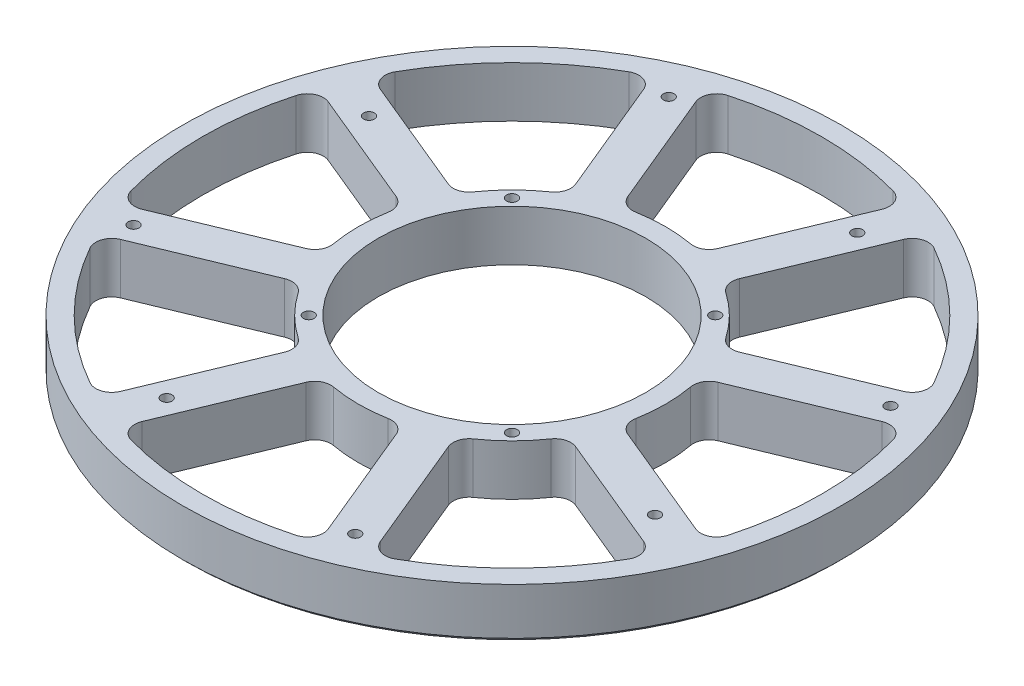
SolidWorks part; units mm, degrees
material "6061-T6 (SS)"
ref_plane "Front Plane" through (0, 0, 0) normal (0, 0, 1) x (1, 0, 0)
ref_plane "Top Plane" through (0, 0, 0) normal (0, 1, 0) x (1, 0, 0)
ref_plane "Right Plane" through (0, 0, 0) normal (1, 0, 0) x (0, 0, -1)
sketch "Sketch2" plane through (0, 0, 0) normal (1, 0, 0) x (0, 0, -1)
  line L0 (0, 0) -> (-82.55, 0)
  line L1 (-82.55, 0) -> (-82.55, 12.7)
  line L2 (-82.55, 12.7) -> (0, 12.7)
  line L5 (0, 12.7) -> (0, 0)
  dimension "D1" = 82.55
  dimension "D2" = 12.7
ref_axis "Axis1" through (0, -0.5, 0) along (0, 1, 0)
revolve "Revolve1" add sketch "Sketch2" angle 360 about axis through (0, -0.5, 0) along (0, 1, 0)
hole_wizard "#6-32 Tapped Hole1" positions "Sketch6" profile "Sketch7" tap size "#6-32" standard "ANSI Inch" end condition through all
sketch "Sketch6" plane through (0, 12.7, 0) normal (0, 1, 0) x (1, 0, 0)
  line L0 (0, 0) -> (-53.438, 129.0108) construction
  line L2 (0, 0) -> (0, 109.0908) construction
  line L3 (0, 0) -> (-76.2663, 31.5905) construction
  line L4 (0, 0) -> (-68.4315, 68.4315) construction
  circle A0 centre (0, 0) radius 82.55 construction
  point P0 (-27.7637, 67.0275)
  point P18 (-61.1608, 25.3336)
  point P27 (-25.4558, 25.4558)
  dimension "D1" = 22.5
  dimension "D2" = 72.55
  dimension "D3" = 45
  dimension "D4" = 66.2
  dimension "D6" = 22.5
  dimension "D5" = 36
sketch "Sketch7" plane through (-27.7637, 12.7, -67.0275) normal (1, 0, 0) x (0, 0, 1)
  line L0 (0, 0) -> (0, 12.7)
  line L1 (0, 12.7) -> (1.3525, 12.7)
  line L2 (1.3525, 12.7) -> (1.3525, 0)
  line L5 (1.3525, 0) -> (0, 0)
  line L11 (0, -6.35) -> (0, 107.95) construction
  dimension "Thread Major Dia." = 2.7051
  dimension "Thru Tap Drill Depth" = 12.7
pattern_circular "CirPattern3" count 4 over 360 about axis through (0, -0.5, 0) along (0, 1, 0) of "#6-32 Tapped Hole1"
sketch "Sketch8" plane through (0, 12.7, 0) normal (0, 1, 0) x (1, 0, 0)
  line L4 (0, 0) -> (0, 93.9995) construction
  line L5 (0, 0) -> (113.8372, 0) construction
  line L6 (-9.9891, 37.1815) -> (-24.996, 73.4112)
  line L7 (9.9891, 37.1815) -> (24.996, 73.4112)
  line L8 (0, 0) -> (-27.7637, 67.0275) construction
  arc A0 (-9.9891, 37.1815) -> (9.9891, 37.1815) centre (0, 0) cw
  arc A1 (-24.996, 73.4112) -> (24.996, 73.4112) centre (0, 0) cw
  circle A2 centre (0, 0) radius 82.55 construction
  dimension "D1" = 38.5
  dimension "D2" = 5
  dimension "D3" = 5
extrude "Cut-Extrude1" cut sketch "Sketch8" against normal through all
fillet "Fillet1" radius 4 4 edges at (9.9891, 6.35, -37.1815) (24.996, 6.35, -73.4112) (-9.9891, 6.35, -37.1815) (-24.996, 6.35, -73.4112)
pattern_circular "CirPattern4" count 8 over 360 about axis through (0, -0.5, 0) along (0, 1, 0) of "Cut-Extrude1", "Fillet1"
chamfer "Chamfer2" distance 1 angle 45 1 edges at (0, 0, -82.55)
sketch "Sketch9" plane through (0, 12.7, 0) normal (0, 1, 0) x (1, 0, 0)
  circle A0 centre (0, 0) radius 33.5
  dimension "D1" = 67
extrude "Cut-Extrude2" cut sketch "Sketch9" against normal through all
equation "\"TubeDiameter\" = 6.500in"
equation "\"D1@Sketch2\"=\"TubeDiameter\"/2"
equation "\"D2@Sketch6\"=\"TubeDiameter\"/2-10mm"
